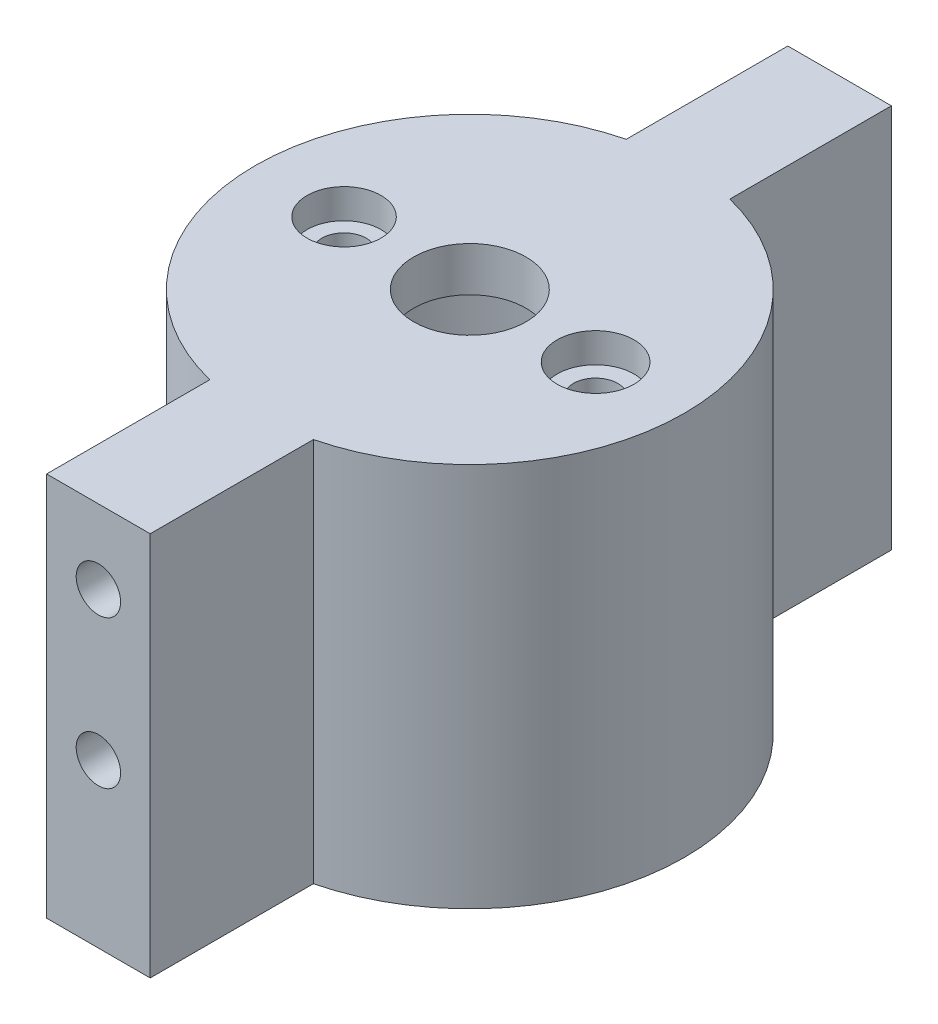
SolidWorks part; units mm, degrees
other "Markup1"
sketch "Sketch11" plane through (-17.3474, -40, -17.5082) normal (-0.1763, -0.9804, -0.0883) x (-0.1909, 0.1221, -0.974)
ref_plane "Front Plane" through (0, 0, 0) normal (0, 0, 1) x (1, 0, 0)
ref_plane "Top Plane" through (0, 0, 0) normal (0, 1, 0) x (1, 0, 0)
ref_plane "Right Plane" through (0, 0, 0) normal (1, 0, 0) x (0, 0, -1)
sketch "Sketch1" plane through (0, 0, 0) normal (0, 1, 0) x (1, 0, 0)
  circle A0 centre (0, 0) radius 14.5
extrude "Boss-Extrude1" add sketch "Sketch1" along normal blind 2 contours A0
sketch "Sketch2" plane through (0, 2, 0) normal (0, 1, 0) x (1, 0, 0)
  line L0 (0, 0) -> (-8.5, 0) construction
  line L1 (0, 0) -> (0, -2.0986) construction
  circle A0 centre (0, 0) radius 3.8
  circle A1 centre (-8.5, 0) radius 1.5
  circle A2 centre (8.5, 0) radius 1.5
  dimension "D1" = 8.5
extrude "Cut-Extrude1" cut sketch "Sketch2" against normal blind 2.5
sketch "Sketch3" plane through (0, 0, 0) normal (0, -1, 0) x (1, 0, 0)
  circle A0 centre (0, 0) radius 14.5
  circle A1 centre (0, 0) radius 12.5
  circle M3 centre (8.5, 0) radius 1.5
  circle M4 centre (-8.5, 0) radius 1.5
  circle M5 centre (0, 0) radius 3.8
  dimension "D1" = 2
extrude "Boss-Extrude2" add sketch "Sketch3" along normal blind 23 contours A1 M3 M5 M4 | A0 region at (-12.1464, 0, 0)
sketch "Sketch4" plane through (0, 2, 0) normal (0, 1, 0) x (1, 0, 0)
  circle A0 centre (0, 0) radius 3.8
  circle A1 centre (8.5, 0) radius 1.5
  circle A2 centre (-8.5, 0) radius 1.5
  circle A3 centre (0, 0) radius 14.5
extrude "Boss-Extrude3" add sketch "Sketch4" along normal blind 1 contours A3 | A2 | A1 | A0
sketch "Sketch5" plane through (0, 3, 0) normal (0, 1, 0) x (1, 0, 0)
  line L0 (0, 0) -> (0, 9.3425) construction
  circle A0 centre (8.5, 0) radius 2.6
  circle A1 centre (-8.5, 0) radius 2.5
extrude "Cut-Extrude2" cut sketch "Sketch5" against normal blind 2
sketch "Sketch12" plane through (0, -23, 0) normal (0, -1, 0) x (1, 0, 0)
  line L0 (0, -14.5) -> (0, -25.1) construction
  line L1 (3.5, -25.1) -> (-3.5, -25.1)
  line L2 (-3.5, -25.1) -> (-3.5, -14.0712)
  line L3 (3.5, -25.1) -> (3.5, -14.0712)
  circle A0 centre (0, 0) radius 14.5 construction
  arc A1 (-3.5, -14.0712) -> (3.5, -14.0712) centre (0, 0) ccw
  dimension "D1" = 10.6
  dimension "D2" = 3.5
extrude "Boss-Extrude4" add sketch "Sketch12" against normal blind 26
sketch "Sketch14" plane through (0, 0, -25.1) normal (0, 0, -1) x (-1, 0, 0)
  line L0 (-14.5, -23) -> (14.5, -23) construction
  line L1 (-3.5, 3) -> (3.5, 3)
  line L2 (-3.5, 3) -> (-3.5, -23)
  line L3 (-3.5, -23) -> (3.5, -23)
  line L4 (3.5, 3) -> (3.5, -23)
  line L5 (3.5, 3) -> (3.5, -23) construction
extrude "Cut-Extrude3" cut sketch "Sketch14" against normal blind 0.11 contours L2 L1 L4 L3
sketch "Sketch16" plane through (0, 0, -24.99) normal (0, 0, -1) x (-1, 0, 0)
  line L0 (0, 3) -> (0, -2) construction
  line L1 (-3.5, 3) -> (3.5, 3) construction
  line L2 (0, -2) -> (0, -12) construction
  circle A0 centre (0, -2) radius 1.5
  circle A1 centre (0, -12) radius 1.5
  dimension "D1" = 5
  dimension "D2" = 10
extrude "Cut-Extrude4" cut sketch "Sketch16" against normal blind 6
sketch "Sketch17" plane through (0, 3, 0) normal (0, 1, 0) x (1, 0, 0)
  line L0 (0, 0) -> (0, 24.99) construction
  line L1 (3.5, 24.99) -> (-3.5, 24.99) construction
sketch "Sketch18" plane through (0, -23, 0) normal (0, -1, 0) x (1, 0, 0)
  line L0 (0, 14.5) -> (0, 25.1) construction
  line L1 (3.5, 25.1) -> (-3.5, 25.1)
  line L2 (-3.5, 25.1) -> (-3.5, 14.0712)
  line L3 (3.5, 25.1) -> (3.5, 14.0712)
  arc A0 (3.5, -14.0712) -> (-3.5, -14.0712) centre (0, 0) ccw construction
  arc A1 (3.5, 14.0712) -> (-3.5, 14.0712) centre (0, 0) ccw
  dimension "D1" = 10.6
  dimension "D2" = 3.5
extrude "Boss-Extrude5" add sketch "Sketch18" against normal through all contours A1 L2 L1 L3
sketch "Sketch19" plane through (0, 0, 25.1) normal (0, 0, 1) x (1, 0, 0)
  line L0 (-3.5, 3) -> (3.5, 3) construction
  line L1 (0, 3) -> (0, -2) construction
  line L2 (0, -2) -> (0, -12) construction
  circle A0 centre (0, -2) radius 1.5
  circle A1 centre (0, -12) radius 1.5
  dimension "D1" = 5
  dimension "D2" = 10
extrude "Cut-Extrude5" cut sketch "Sketch19" against normal blind 5
